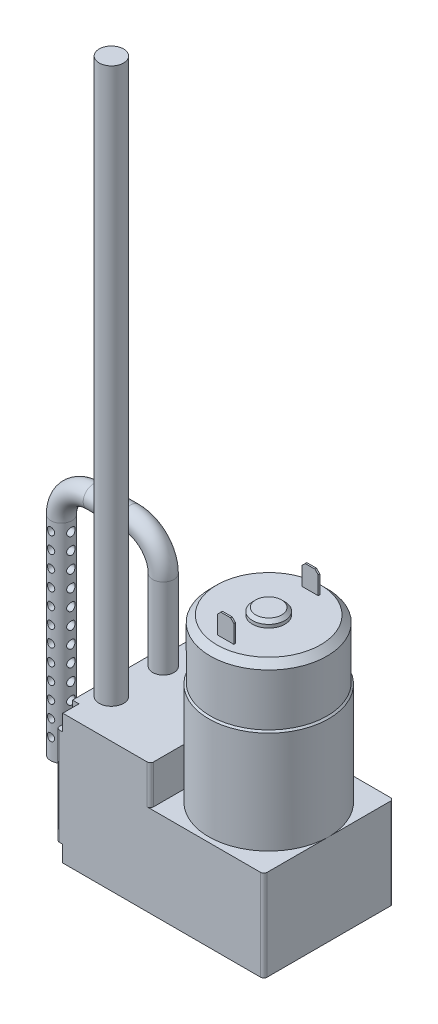
SolidWorks part; units mm, degrees
material "5052-H32"
ref_plane "Front Plane" through (0, 0, 0) normal (0, 0, 1) x (1, 0, 0)
ref_plane "Top Plane" through (0, 0, 0) normal (0, 1, 0) x (1, 0, 0)
ref_plane "Right Plane" through (0, 0, 0) normal (1, 0, 0) x (0, 0, -1)
sketch "Sketch1" plane through (0, 0, 0) normal (0, 1, 0) x (1, 0, 0)
  line L1 (-32, 20) -> (32, 20)
  line L2 (-32, 20) -> (-32, -20)
  line L3 (-32, -20) -> (32, -20)
  line L4 (32, 20) -> (32, -20)
  line L5 (-32, 20) -> (32, -20) construction
  line L6 (-32, -20) -> (32, 20) construction
  point P0 (0, 0)
  dimension "D1" = 64
  dimension "D2" = 40
extrude "Boss-Extrude1" add sketch "Sketch1" along normal blind 40
sketch "Sketch2" plane through (0, 40, 0) normal (0, 1, 0) x (1, 0, 0)
  line L0 (32, 20) -> (-32, 20) construction
  line L1 (-3, 20) -> (32, 20)
  line L2 (-3, 20) -> (-3, -20)
  line L3 (-3, -20) -> (32, -20)
  line L4 (32, 20) -> (32, -20)
  dimension "D1" = 35
extrude "Cut-Extrude1" cut sketch "Sketch2" against normal blind 12
sketch "Sketch3" plane through (0, 28, 0) normal (0, 1, 0) x (1, 0, 0)
  line L0 (32, -20) -> (32, 20) construction
  circle A0 centre (13.5, 0) radius 19
  point P0 (13.5, 0)
  dimension "D2" = 38
  dimension "D1" = 18.5
extrude "Cut-Extrude2" cut sketch "Sketch3" along normal through all
sketch "Sketch4" plane through (0, 28, 0) normal (0, 1, 0) x (1, 0, 0)
  line L0 (32, -20) -> (32, 20) construction
  circle A0 centre (13.5, 0) radius 18.5
  dimension "D2" = 37
  dimension "D1" = 18.5
extrude "Boss-Extrude2" add sketch "Sketch4" along normal blind 30
sketch "Sketch5" plane through (0, 58, 0) normal (0, 1, 0) x (1, 0, 0)
  circle A0 centre (13.5, 0) radius 18
  dimension "D1" = 36
extrude "Boss-Extrude3" add sketch "Sketch5" along normal blind 20
chamfer "Chamfer1" distance 2 angle 45 2 edges at (13.5, 58, 18) (13.5, 78, 18)
sketch "Sketch6" plane through (0, 78, 0) normal (0, 1, 0) x (1, 0, 0)
  line L1 (11, 13.25) -> (16, 13.25)
  line L2 (11, 13.25) -> (11, 12.75)
  line L3 (11, 12.75) -> (16, 12.75)
  line L4 (16, 13.25) -> (16, 12.75)
  line L5 (11, 13.25) -> (16, 12.75) construction
  line L6 (11, 12.75) -> (16, 13.25) construction
  line L7 (11, -12.75) -> (16, -12.75)
  line L8 (11, -12.75) -> (11, -13.25)
  line L9 (11, -13.25) -> (16, -13.25)
  line L10 (16, -12.75) -> (16, -13.25)
  line L11 (11, -12.75) -> (16, -13.25) construction
  line L12 (11, -13.25) -> (16, -12.75) construction
  point P0 (13.5, 13)
  point P5 (13.5, -13)
  point P11 (13.5, 0)
  dimension "D1" = 26
  dimension "D2" = 0.5
  dimension "D3" = 0.5
  dimension "D4" = 5
  dimension "D5" = 5
  dimension "D6" = 13
extrude "Boss-Extrude4" add sketch "Sketch6" along normal blind 6.6
chamfer "Chamfer2" distance 1 angle 45 4 edges at (16, 84.6, 13) (11, 84.6, 13) (11, 84.6, -13) (16, 84.6, -13)
sketch "Sketch7" plane through (0, 40, 0) normal (0, 1, 0) x (1, 0, 0)
  line L0 (-32, 20) -> (-32, -20) construction
  circle A0 centre (-27, 8) radius 2.5
  circle A1 centre (-27, -8) radius 2.5
  dimension "D1" = 16
  dimension "D2" = 5
  dimension "D4" = 5
  dimension "D3" = 8
extrude "Boss-Extrude5" add sketch "Sketch7" along normal blind 12
chamfer "Chamfer3" distance 1 angle 45 2 edges at (-27, 52, 10.5) (-27, 52, -5.5)
sketch "Sketch9" plane through (-32, 0, 0) normal (-1, 0, 0) x (0, 0, 1)
  line L1 (-5, 33) -> (-8, 30)
  line L3 (-8, 52) -> (-8, 0) construction
  line L4 (-6.5, 52) -> (-9.5, 52) construction
  line L5 (-20, 0) -> (20, 0) construction
  line L6 (8, 52) -> (8, 0) construction
  line L7 (9.5, 52) -> (6.5, 52) construction
  line L8 (-7, 37) -> (-9, 37)
  line L9 (-9, 37) -> (-9, 33)
  line L10 (-9, 33) -> (-11, 33)
  line L11 (-11, 33) -> (-8, 30)
  line L12 (-7, 33) -> (-5, 33)
  line L13 (-20, 40) -> (20, 40) construction
  line L14 (-7, 37) -> (-7, 33)
  line L23 (9, 30) -> (9, 34)
  line L24 (9, 34) -> (11, 34)
  line L25 (5, 34) -> (8, 37)
  line L26 (7, 34) -> (5, 34)
  line L27 (7, 30) -> (7, 34)
  line L28 (9, 30) -> (7, 30)
  line L29 (11, 34) -> (8, 37)
  point P20 (-8, 37)
  point P39 (8, 20.0991)
  dimension "D1" = 1
  dimension "D2" = 4
  dimension "D3" = 3
  dimension "D4" = 45
  dimension "D5" = 3
  dimension "D6" = 3
extrude "Cut-Extrude3" cut sketch "Sketch9" against normal blind 0.1
fillet "Fillet1" radius 1 8 edges at (-3, 34, -9.4207) (-3, 34, 9.4207) (-3, 34, 20) (-3, 34, -20) (-32, 20, -20) (32, 14, -20) (32, 14, 20) (-32, 20, 20)
sketch "Sketch10" plane through (0, 78, 0) normal (0, 1, 0) x (1, 0, 0)
  circle A0 centre (13.5, 0) radius 5
  dimension "D1" = 10
extrude "Boss-Extrude6" add sketch "Sketch10" along normal blind 2
chamfer "Chamfer4" distance 1 angle 45 1 edges at (13.5, 80, 5)
sketch "Sketch13" plane through (-32, 0, 0) normal (-1, 0, 0) x (0, 0, 1)
  line L1 (-20, 40) -> (-15, 40)
  line L2 (-20, 40) -> (-20, 35)
  line L3 (-20, 35) -> (-17, 35)
  line L4 (-15, 40) -> (-15, 37)
  line L5 (20, 40) -> (15, 40)
  line L6 (20, 40) -> (20, 35)
  line L7 (20, 35) -> (17, 35)
  line L8 (15, 40) -> (15, 37)
  line L9 (-20, 0) -> (-15, 0)
  line L10 (-20, 0) -> (-20, 5)
  line L11 (-20, 5) -> (-17, 5)
  line L12 (-15, 0) -> (-15, 3)
  line L13 (20, 0) -> (15, 0)
  line L14 (20, 0) -> (20, 5)
  line L15 (20, 5) -> (17, 5)
  line L16 (15, 0) -> (15, 3)
  arc A0 (-17, 5) -> (-15, 3) centre (-17, 3) cw
  arc A1 (17, 5) -> (15, 3) centre (17, 3) ccw
  arc A2 (17, 35) -> (15, 37) centre (17, 37) cw
  arc A3 (-17, 35) -> (-15, 37) centre (-17, 37) ccw
  dimension "D9" = 2
  dimension "D1" = 5
  dimension "D2" = 5
  dimension "D3" = 5
  dimension "D4" = 5
  dimension "D5" = 5
  dimension "D6" = 5
  dimension "D7" = 5
  dimension "D8" = 5
extrude "Cut-Extrude4" cut sketch "Sketch13" against normal blind 2
sketch3d "3DSketch1"
  line L0 (-27, 52, -8) -> (-27, 64.8548, -8)
  line L1 (-27, 51, -8) -> (-27, 52, -8) construction
  line L2 (-37, 74.8548, -8) -> (-48.4136, 74.8548, -8)
  line L3 (-58.4136, 64.8548, -8) -> (-58.4136, 0.743, -8)
  arc A0 (-27, 64.8548, -8) -> (-37, 74.8548, -8) centre (-37, 64.8548, -8) ccw
  arc A1 (-48.4136, 74.8548, -8) -> (-58.4136, 64.8548, -8) centre (-48.4136, 64.8548, -8) ccw
  point P12 (-27, 74.8548, -8)
  point P13 (-37, 64.8548, 2)
  point P16 (-58.4136, 74.8548, -8)
  point P17 (-48.4136, 64.8548, 2)
  dimension "D1" = 10
sketch "Sketch15" plane through (0, 52, 0) normal (0, 1, 0) x (1, 0, 0)
  circle A0 centre (-27, 8) radius 3.2867
sweep "Sweep1" add profiles "Sketch15" path "3DSketch1"
sketch "Sketch16" plane through (0, 52, 0) normal (0, -1, 0) x (1, 0, 0)
  circle A1 centre (-27, -8) radius 3.2867
  circle A2 centre (-27, -8) radius 3.2867
  dimension "D1" = 0
extrude "Boss-Extrude7" add sketch "Sketch16" along normal up to surface (12 mm away) up to face at (-15.1535, 40, 0)
sketch "Sketch17" plane through (0, 0, 0) normal (0, 0, 1) x (1, 0, 0)
  circle A1 centre (-58.4946, 62.0086) radius 1.1425
  circle A2 centre (-58.4946, 57.0086) radius 1.1425
  circle A3 centre (-58.4946, 52.0086) radius 1.1425
  circle A4 centre (-58.4946, 47.0086) radius 1.1425
  circle A5 centre (-58.4946, 42.0086) radius 1.1425
  circle A6 centre (-58.4946, 37.0086) radius 1.1425
  circle A7 centre (-58.4946, 32.0086) radius 1.1425
  circle A8 centre (-58.4946, 27.0086) radius 1.1425
  circle A9 centre (-58.4946, 22.0086) radius 1.1425
  circle A10 centre (-58.4946, 17.0086) radius 1.1425
  circle A11 centre (-58.4946, 12.0086) radius 1.1425
  circle A12 centre (-58.4946, 7.0086) radius 1.1425
  dimension "D1" = 12
extrude "Cut-Extrude5" cut sketch "Sketch17" against normal blind 12
ref_plane "Plane1" through (-50, 0, 0) normal (1, 0, 0) x (0, 0, -1)
sketch "Sketch18" plane through (-50, 0, 0) normal (1, 0, 0) x (0, 0, -1)
  circle A0 centre (7.88, 61.9332) radius 1.253
  circle A1 centre (7.88, 56.9332) radius 1.253
  circle A2 centre (7.88, 51.9332) radius 1.253
  circle A3 centre (7.88, 46.9332) radius 1.253
  circle A4 centre (7.88, 41.9332) radius 1.253
  circle A5 centre (7.88, 36.9332) radius 1.253
  circle A6 centre (7.88, 31.9332) radius 1.253
  circle A7 centre (7.88, 26.9332) radius 1.253
  circle A8 centre (7.88, 21.9332) radius 1.253
  circle A9 centre (7.88, 16.9332) radius 1.253
  circle A10 centre (7.88, 11.9332) radius 1.253
  circle A11 centre (7.88, 6.9332) radius 1.253
  dimension "D1" = 12
extrude "Cut-Extrude6" cut sketch "Sketch18" against normal blind 12
sketch "Sketch19" plane through (0, 40, 0) normal (0, 1, 0) x (1, 0, 0)
  circle A0 centre (-27, -8) radius 3.762
extrude "Boss-Extrude8" add sketch "Sketch19" along normal blind 171
